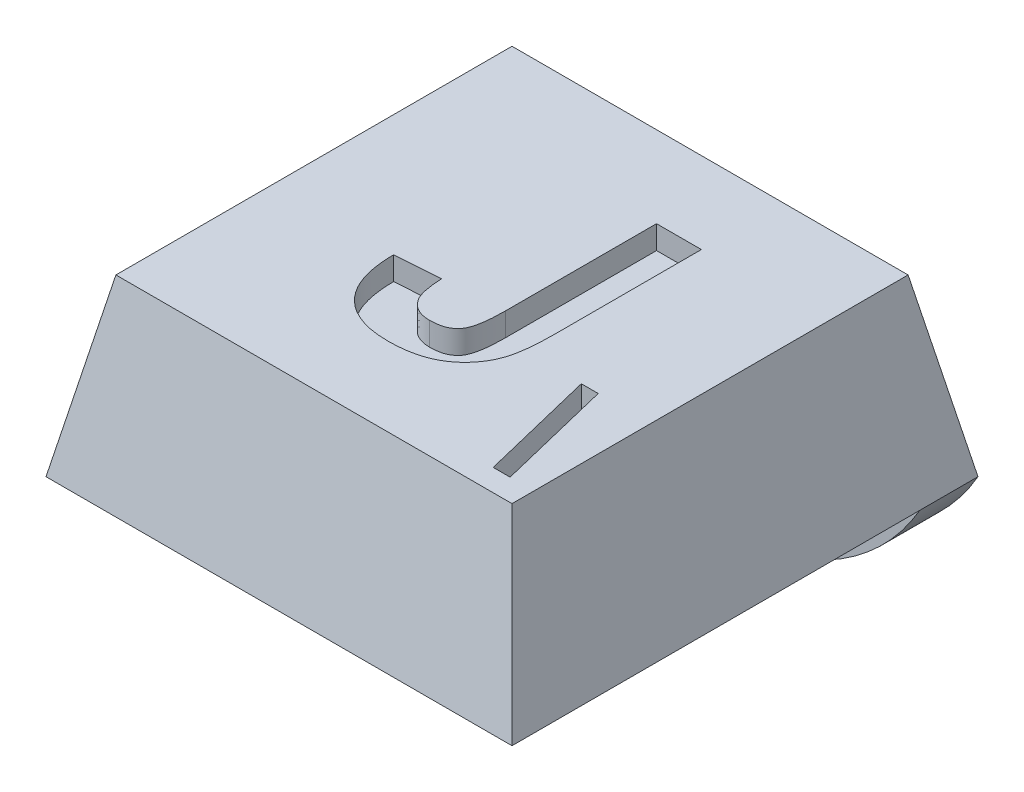
SolidWorks part; units mm, degrees
ref_plane "Front Plane" through (0, 0, 0) normal (0, 0, 1) x (1, 0, 0)
ref_plane "Top Plane" through (0, 0, 0) normal (0, 1, 0) x (1, 0, 0)
ref_plane "Right Plane" through (0, 0, 0) normal (1, 0, 0) x (0, 0, -1)
sketch "Sketch1" plane through (0, 0, 0) normal (0, 1, 0) x (1, 0, 0)
  line L1 (0, 0) -> (8, 0)
  line L2 (0, 0) -> (0, 8)
  line L3 (0, 8) -> (8, 8)
  line L4 (8, 0) -> (8, 8)
  dimension "D1" = 8
  dimension "D2" = 8
extrude "Boss-Extrude1" add sketch "Sketch1" along normal blind 3
sketch "Sketch2" plane through (0, 0, 0) normal (0, 0, 1) x (1, 0, 0)
  line L0 (0, 0) -> (0.6, 3)
  line L1 (0, 3) -> (8, 3) construction
  line L2 (0.6, 3) -> (0, 3)
  line L3 (0, 3) -> (0, 0)
  line L4 (8, 0) -> (7.4, 3)
  line L5 (7.4, 3) -> (8, 3)
  line L6 (8, 3) -> (8, 0)
  dimension "D1" = 0.6
  dimension "D2" = 0.6
extrude "Cut-Extrude1" cut sketch "Sketch2" against normal through all both and the other way through all
sketch "Sketch3" plane through (0, 0, 0) normal (1, 0, 0) x (0, 0, -1)
  line L0 (0, 0) -> (0.6, 3)
  line L1 (8, 3) -> (0, 3) construction
  line L2 (0.6, 3) -> (0, 3)
  line L3 (0, 3) -> (0, 0)
  line L4 (8, 3) -> (7.4, 3)
  line L5 (7.4, 3) -> (8, 0)
  line L6 (8, 3) -> (8, 0)
  dimension "D1" = 0.6
  dimension "D2" = 0.6
extrude "Cut-Extrude2" cut sketch "Sketch3" along normal blind 11
sketch "Sketch4" plane through (0, 0, 0) normal (0, -1, 0) x (1, 0, 0)
  line L0 (8, 0) -> (8, -8) construction
  line L3 (0, 0) -> (8, 0) construction
  circle A0 centre (4, -3.75) radius 1.8
  dimension "D1" = 3.6
  dimension "D2" = 4
  dimension "D3" = 3.75
extrude "Cut-Extrude3" cut sketch "Sketch4" against normal blind 0.8
sketch "Sketch5" plane through (0, 0, 0) normal (0, -1, 0) x (1, 0, 0)
  line L0 (8, 0) -> (8, -8) construction
  line L1 (0, -8) -> (8, -8)
  line L2 (0, -8) -> (0, -7)
  line L3 (0, -7) -> (8, -7)
  line L4 (8, -8) -> (8, -7)
  dimension "D1" = 1
extrude "Boss-Extrude2" add sketch "Sketch5" along normal blind 2
fillet "Fillet1" radius 4 2 edges at (8, -2, -7.5) (0, -2, -7.5)
sketch "Sketch6" plane through (0, 3, 0) normal (0, 1, 0) x (1, 0, 0)
  text T0 "J" font "Arial" height 4
extrude "Cut-Extrude4" cut sketch "Sketch6" against normal blind 0.4
sketch "Sketch7" plane through (0, 3, 0) normal (0, 1, 0) x (1, 0, 0)
  text T0 "\\" font "Arial" height 2
extrude "Cut-Extrude5" cut sketch "Sketch7" against normal blind 0.4
